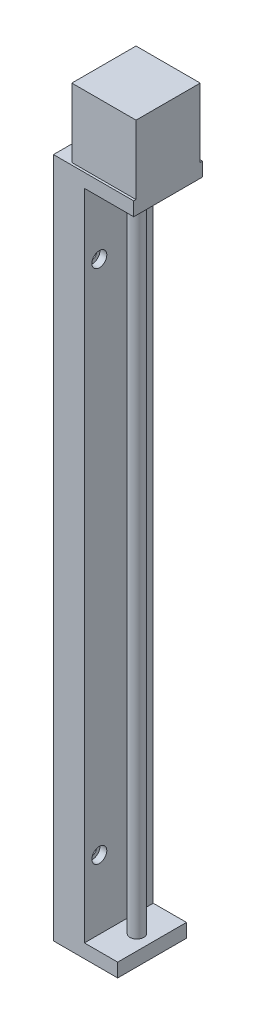
SolidWorks part; units mm, degrees
ref_plane "Front Plane" through (0, 0, 0) normal (0, 0, 1) x (1, 0, 0)
ref_plane "Top Plane" through (0, 0, 0) normal (0, 1, 0) x (1, 0, 0)
ref_plane "Right Plane" through (0, 0, 0) normal (1, 0, 0) x (0, 0, -1)
sketch "Sketch1" plane through (0, 0, 0) normal (0, 0, 1) x (1, 0, 0)
  line L0 (-10.5, 178.5) -> (-10.5, 148.5)
  line L1 (17.5, -142.5) -> (-17.5, -142.5)
  line L2 (17.5, -142.5) -> (17.5, 142.5)
  line L3 (17.5, 142.5) -> (-17.5, 142.5)
  line L4 (-17.5, -142.5) -> (-17.5, 142.5)
  line L5 (17.5, -142.5) -> (-17.5, 142.5) construction
  line L6 (17.5, 142.5) -> (-17.5, -142.5) construction
  line L7 (-17.5, -142.5) -> (10.5, -142.5)
  line L8 (-17.5, -142.5) -> (-17.5, -148.5)
  line L9 (-17.5, -148.5) -> (10.5, -148.5)
  line L10 (10.5, -142.5) -> (10.5, -148.5)
  line L11 (-17.5, 142.5) -> (17.5, 142.5)
  line L12 (-17.5, 142.5) -> (-17.5, 148.5)
  line L13 (-17.5, 148.5) -> (17.5, 148.5)
  line L14 (17.5, 142.5) -> (17.5, 148.5)
  line L15 (-17.5, 148.5) -> (17.5, 148.5)
  line L17 (-10.5, 178.5) -> (17.5, 178.5)
  line L18 (17.5, 148.5) -> (17.5, 178.5)
  line L19 (-4, 142.5) -> (-4, -142.5)
  point P0 (0, 0)
  dimension "D1" = 285
  dimension "D2" = 6
  dimension "D3" = 6
  dimension "D4" = 30
  dimension "D5" = 28
  dimension "D6" = 35
  dimension "D7" = 13.5
  dimension "D8" = 28
extrude "Boss-Extrude1" add sketch "Sketch1" along normal mid plane 30 contours L3 L14 L13 L12 L11 | L19 L11 L4 L7 | L10 L1 L7 L8 L9 region at (0, 145.5, 0) region at (-10.75, 0, 0) region at (-3.5, -145.5, 0)
extrude "Boss-Extrude2" add sketch "Sketch1<3>" along normal mid plane 28 contours L13 L18 L17 L0 region at (3.5, 163.5, 0)
sketch "Sketch1<3>" plane through (0, 0, 0) normal (0, 0, 1) x (1, 0, 0) same geometry as "Sketch1"
sketch "Sketch2" plane through (0, -142.5, 0) normal (0, 1, 0) x (1, 0, 0)
  line L0 (-4, 0) -> (10.5, 0) construction
  line L1 (-4, -15) -> (-4, 15) construction
  line L2 (10.5, -15) -> (10.5, 15) construction
  circle A0 centre (3.87, 0) radius 3
  dimension "D1" = 6
  dimension "D2" = 7.87
extrude "Boss-Extrude3" add sketch "Sketch2" along normal up to surface (285 mm away) up to face at (6.75, 142.5, 0)
hole_wizard "CBORE for M3 SHCS1" positions "Sketch8" profile "Sketch10" counterbore size "M3" standard "ANSI Metric" end condition through all
sketch "Sketch8" plane through (-4, 0, 0) normal (1, 0, 0) x (0, 0, -1)
  line L0 (-15, 148.5) -> (15, 148.5) construction
  line L1 (-15, 148.5) -> (15, 148.5) construction
  line L2 (0, 148.5) -> (0, 147.4581) construction
  point P0 (-8.5, 112.5)
  point P2 (8.5, 112.5)
  point P4 (8.5, -112.5)
  point P6 (-8.5, -112.5)
  dimension "D1" = 36
  dimension "D2" = 225
  dimension "D3" = 17
sketch "Sketch10" plane through (-4, 112.5, 8.5) normal (0, 1, 0) x (0, 0, -1)
  line L0 (0, 0) -> (0, 13.5)
  line L1 (0, 13.5) -> (1.7, 13.5)
  line L3 (1.7, 13.5) -> (1.7, 3)
  line L4 (1.7, 3) -> (3.25, 3)
  line L5 (3.25, 3) -> (3.25, 0)
  line L7 (3.25, 0) -> (0, 0)
  line L11 (0, -6.35) -> (0, 107.95) construction
  dimension "Thru Hole Dia." = 3.4
  dimension "Thru Hole Depth" = 13.5
  dimension "C'Bore Dia." = 6.5
  dimension "C'Bore Depth" = 3
